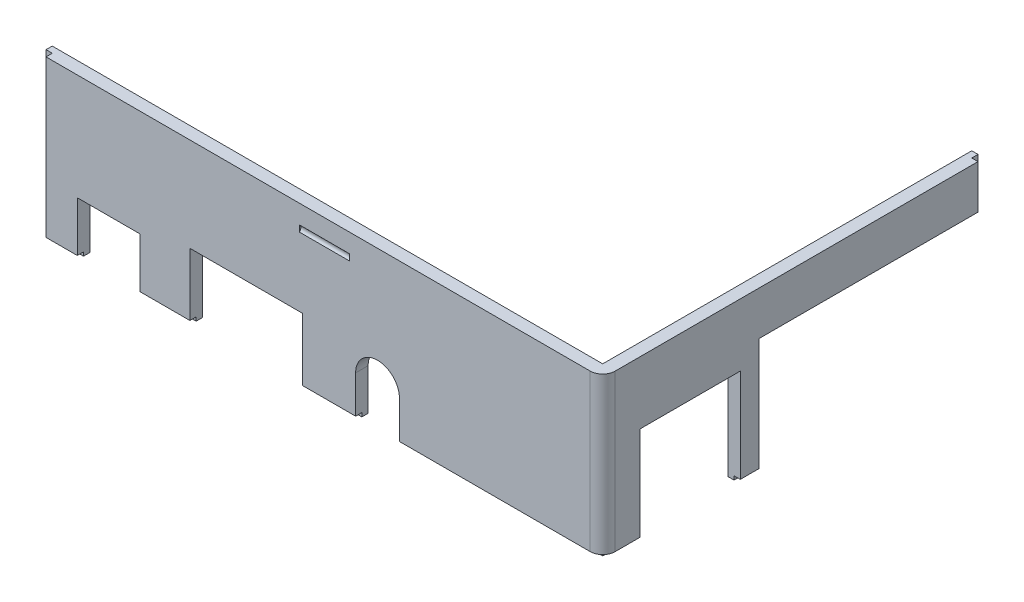
SolidWorks part; units mm, degrees
ref_plane "Přední rovina" through (0, 0, 0) normal (0, 0, 1) x (1, 0, 0)
ref_plane "Horní rovina" through (0, 0, 0) normal (0, 1, 0) x (1, 0, 0)
ref_plane "Pravá rovina" through (0, 0, 0) normal (1, 0, 0) x (0, 0, -1)
sketch "Skica1" plane through (0, 0, 0) normal (0, 1, 0) x (1, 0, 0)
  line L1 (0, 0) -> (90, 0)
  line L2 (0, 0) -> (0, 2)
  line L3 (0, 2) -> (90, 2)
  line L4 (90, 0) -> (90, 2)
  line L9 (90, 2) -> (88, 2)
  line L10 (90, 2) -> (90, 61)
  line L11 (90, 61) -> (88, 61)
  line L12 (88, 2) -> (88, 61)
  line L17 (0, 0) -> (1, 0)
  line L18 (0, 0) -> (0, 1)
  line L19 (0, 1) -> (1, 1)
  line L20 (1, 0) -> (1, 1)
  line L21 (90, 61) -> (89, 61)
  line L22 (90, 61) -> (90, 60)
  line L23 (90, 60) -> (89, 60)
  line L24 (89, 61) -> (89, 60)
  dimension "D1" = 2
  dimension "D2" = 90
  dimension "D3" = 1
  dimension "D4" = 61
  dimension "D5" = 2
  dimension "D6" = 1
extrude "Přidat vysunutím1" add sketch "Skica1" along normal blind 25 contours L24 L11 L12 L3 L10 L23 | L20 L1 L4 L3 L2 L19 region at (45.2486, 0, -1.0028) region at (88.9957, 0, -31.2521)
sketch "Skica2" plane through (0, 0, 0) normal (0, -1, 0) x (1, 0, 0)
  line L0 (0, -1) -> (0, -2) construction
  line L1 (0, -1) -> (88, -1)
  line L2 (0, -1) -> (0, -2)
  line L3 (0, -2) -> (88, -2)
  line L4 (88, -1) -> (88, -2)
  line L5 (89, -61) -> (88, -61)
  line L6 (89, -61) -> (89, -1)
  line L7 (89, -1) -> (88, -1)
  line L8 (88, -61) -> (88, -1)
  line L9 (0, -1) -> (1, -1) construction
extrude "Přidat vysunutím2" add sketch "Skica2" along normal blind 0.6 contours L4 L3 L2 L1 | L8 L5 L6 L7
sketch "Skica5" plane through (0, 0, 0) normal (0, 0, 1) x (1, 0, 0)
  line L0 (1, 25) -> (1, 0) construction
  line L1 (6, 8) -> (16, 8)
  line L2 (6, 8) -> (6, -0.6)
  line L3 (6, -0.6) -> (16, -0.6)
  line L4 (16, 8) -> (16, -0.6)
  line L5 (11, 8) -> (11, -0.7728) construction
  line L6 (1, 0) -> (89, 0) construction
  line L7 (0, -0.6) -> (0, 25) construction
  line L8 (24, -0.6) -> (42, -0.6)
  line L9 (24, -0.6) -> (24, 10)
  line L10 (24, 10) -> (42, 10)
  line L11 (42, -0.6) -> (42, 10)
  line L13 (0, -0.6) -> (88, -0.6) construction
  line L14 (1, 0) -> (90, 0) construction
  line L15 (0, -0.6) -> (89, -0.6) construction
  line L16 (33, 10) -> (33, -0.6) construction
  line L17 (50.5, 6) -> (50.5, -0.6)
  line L18 (57.5, 6) -> (57.5, -0.6)
  line L19 (50.5, -0.6) -> (57.5, -0.6)
  arc A1 (50.5, 6) -> (57.5, 6) centre (54, 6) cw
  dimension "D7" = 7
  dimension "D9" = 6
  dimension "D1" = 8
  dimension "D2" = 10
  dimension "D3" = 10
  dimension "D4" = 32
  dimension "D5" = 18
  dimension "D6" = 10
  dimension "D8" = 54
extrude "Odebrat vysunutím1" cut sketch "Skica5" against normal up to next
sketch "Skica6" plane through (90, 0, 0) normal (1, 0, 0) x (0, 0, -1)
  line L1 (6, -0.6) -> (22, -0.6)
  line L2 (6, -0.6) -> (6, 15)
  line L3 (6, 15) -> (22, 15)
  line L4 (22, -0.6) -> (22, 15)
  line L9 (42, -0.6) -> (61, -0.6)
  line L10 (42, -0.6) -> (42, 18)
  line L11 (42, 18) -> (61, 18)
  line L12 (61, -0.6) -> (61, 18)
  line L13 (14, 15) -> (14, -0.6) construction
  line L18 (25, -0.6) -> (41, -0.6)
  line L19 (25, -0.6) -> (25, 18)
  line L20 (25, 18) -> (41, 18)
  line L21 (41, -0.6) -> (41, 18)
  line L22 (33, 18) -> (33, -0.6) construction
  line L23 (61, 25) -> (61, -0.6) construction
  line L24 (51.5, 18) -> (51.5, -0.6) construction
  line L25 (60, 25) -> (60, 0) construction
  line L28 (61, -0.6) -> (1, -0.6) construction
  line L29 (0, 0) -> (60, 0) construction
  line L30 (60, 0) -> (1, 0) construction
  point P20 (0, 0)
  dimension "D1" = 18
  dimension "D2" = 27
  dimension "D3" = 46
  dimension "D4" = 16
  dimension "D5" = 15
  dimension "D6" = 16
  dimension "D7" = 18
extrude "Odebrat vysunutím2" cut sketch "Skica6" against normal up to next
fillet "Fillet1" radius 2 1 edges at (90, 12.5, 0)
sketch "Sketch1" plane through (90, 0, 0) normal (1, 0, 0) x (0, 0, -1)
  line L0 (0, 21.5) -> (-0.4, 21.5)
  line L1 (0, 0) -> (0, 25) construction
  line L2 (2, 25) -> (60, 25) construction
  line L3 (0, 22) -> (0, 21)
  arc A0 (0, 22) -> (0, 21) centre (-0.4, 21.5) cw
  dimension "D2" = 1
  dimension "D1" = 0.4
  dimension "D3" = 4
extrude "Cut-Extrude1" cut sketch "Sketch1" against normal blind 8 from offset 40.5 contours A0 L3 region at (90, 21.5, -0.0979) offset against normal yes
sketch "Sketch2" plane through (90, 0, 0) normal (1, 0, 0) x (0, 0, -1)
  line L1 (41, 18) -> (42, 18)
  line L2 (41, 18) -> (41, -0.6)
  line L3 (41, -0.6) -> (42, -0.6)
  line L4 (42, 18) -> (42, -0.6)
extrude "Cut-Extrude2" cut sketch "Sketch2" against normal up to next
